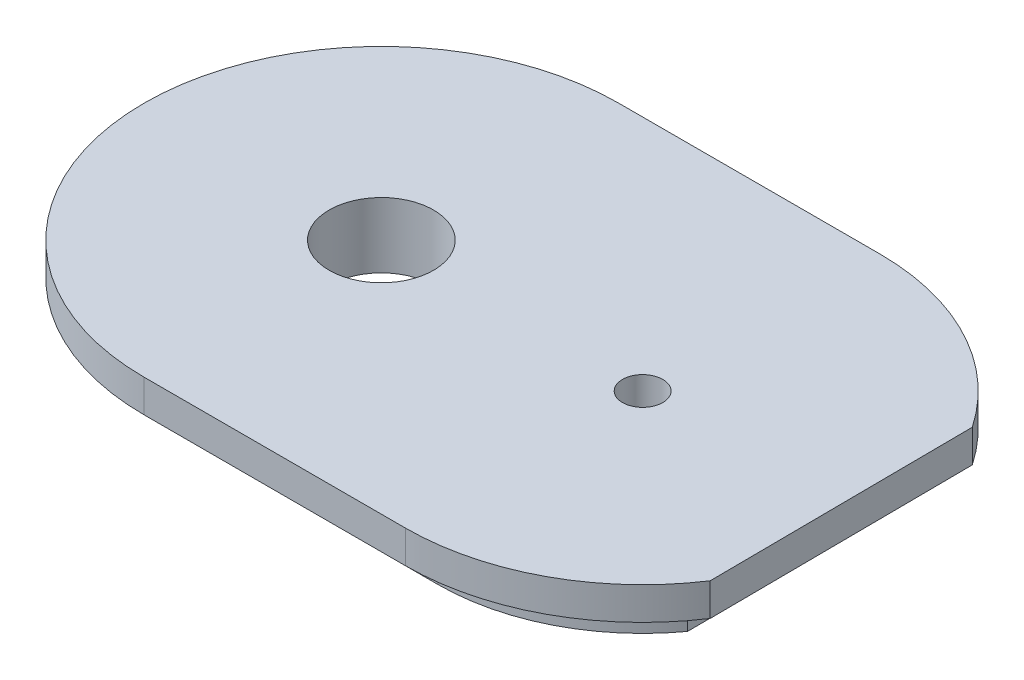
SolidWorks part; units mm, degrees
ref_plane "Front Plane" through (0, 0, 0) normal (0, 0, 1) x (1, 0, 0)
ref_plane "Top Plane" through (0, 0, 0) normal (0, 1, 0) x (1, 0, 0)
ref_plane "Right Plane" through (0, 0, 0) normal (1, 0, 0) x (0, 0, -1)
sketch "Sketch1" plane through (0, 0, 0) normal (0, 1, 0) x (1, 0, 0)
  line L0 (3.2734, 5.1102) -> (3.3472, -5)
  line L2 (-14.2421, -7.8358) -> (-4.2391, -7.8358)
  line L3 (-4.2391, 7.8358) -> (-14.2421, 7.8358)
  line L5 (3.3107, 0) -> (5.1576, 0) construction
  line L6 (2.0943, -4.6138) -> (2.0264, 4.7057)
  line L10 (-4.2391, 9.0858) -> (-14.2421, 9.0858)
  line L11 (-14.2421, -9.0858) -> (-4.2391, -9.0858)
  line L15 (2.0264, 4.7057) -> (2.0943, -4.6138) construction
  line L16 (0, 0) -> (2.0607, 0) construction
  arc A0 (-4.2391, -7.8358) -> (2.0943, -4.6138) centre (-4.2391, 0) ccw
  arc A1 (-14.2421, 7.8358) -> (-14.2421, -7.8358) centre (-14.2421, 0) ccw
  arc A2 (2.0264, 4.7057) -> (-4.2391, 7.8358) centre (-4.2391, 0) ccw
  circle A3 centre (-4.2391, 0) radius 0.77
  arc A6 (3.2734, 5.1102) -> (-4.2391, 9.0858) centre (-4.2391, 0) ccw
  arc A7 (-14.2421, 9.0858) -> (-14.2421, -9.0858) centre (-14.2421, 0) ccw
  arc A8 (-4.2391, -9.0858) -> (3.3472, -5) centre (-4.2391, 0) ccw
  circle A10 centre (-14.2421, 0) radius 2
  dimension "D1" = 1.54
  dimension "D2" = 1.25
extrude "Boss-Extrude2" add sketch "Sketch1" against normal blind 1.25 contours A1 L2 A0 L6 A2 L3 | A10 | A3
extrude "Boss-Extrude3" add sketch "Sketch1<5>" along normal blind 1.25 contours L0 A8 L11 A7 L10 A6 | A10 | A3
sketch "Sketch1<5>" plane through (0, 0, 0) normal (0, 1, 0) x (1, 0, 0) same geometry as "Sketch1"
